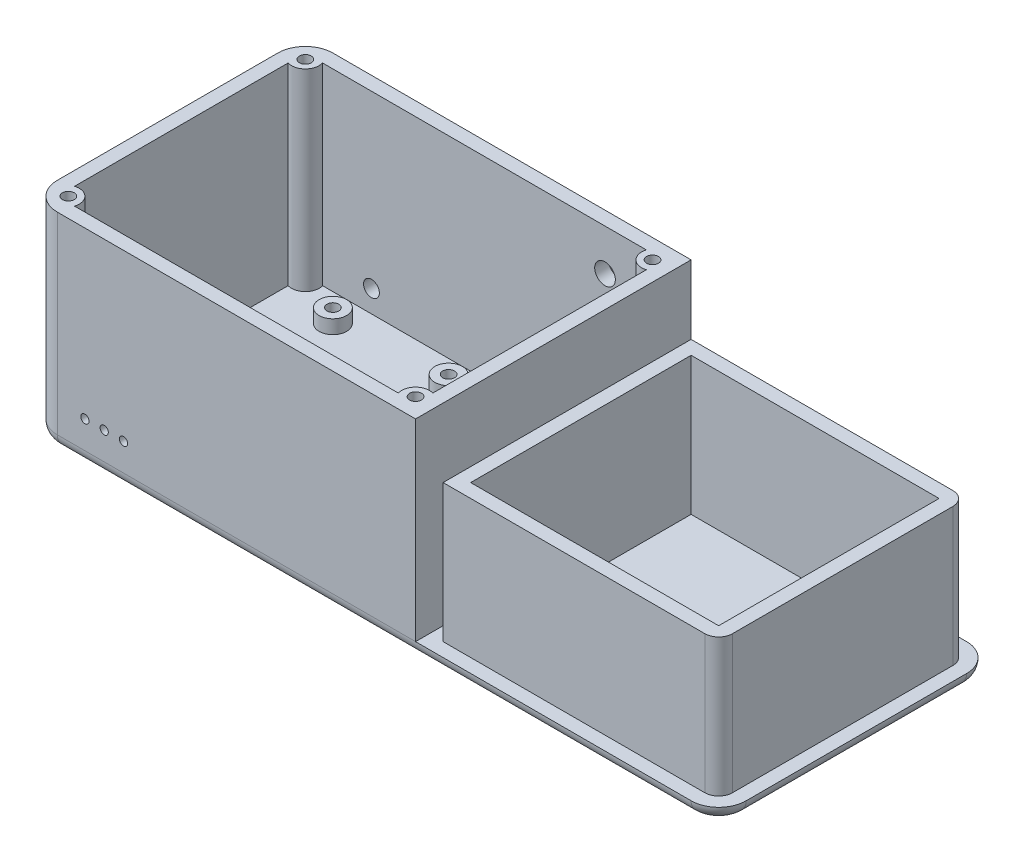
SolidWorks part; units mm, degrees
material "Custom Plastic"
ref_plane "Front Plane" through (0, 0, 0) normal (0, 0, 1) x (1, 0, 0)
ref_plane "Top Plane" through (0, 0, 0) normal (0, 1, 0) x (1, 0, 0)
ref_plane "Right Plane" through (0, 0, 0) normal (1, 0, 0) x (0, 0, -1)
sketch "Sketch1" plane through (0, 0, 0) normal (0, 1, 0) x (1, 0, 0)
  line L1 (-115, -50) -> (115, -50)
  line L2 (-125, -40) -> (-125, 40)
  line L3 (-115, 50) -> (115, 50)
  line L4 (125, -40) -> (125, 40)
  line L5 (-125, -50) -> (125, 50) construction
  line L6 (-125, 50) -> (125, -50) construction
  arc A0 (-115, -50) -> (-125, -40) centre (-115, -40) cw
  arc A1 (115, -50) -> (125, -40) centre (115, -40) ccw
  arc A2 (115, 50) -> (125, 40) centre (115, 40) cw
  arc A3 (-125, 40) -> (-115, 50) centre (-115, 40) cw
  point P0 (0, 0)
  dimension "D3" = 10
  dimension "D1" = 250
  dimension "D2" = 100
extrude "Boss-Extrude1" add sketch "Sketch1" along normal blind 5
fillet "Fillet1" radius 5 8 edges at (0, 0, 50) (122.0711, 0, 47.0711) (125, 0, 0) (122.0711, 0, -47.0711) (0, 0, -50) (-122.0711, 0, -47.0711) (-125, 0, 0) (-122.0711, 0, 47.0711)
sketch "Sketch2" plane through (0, 5, 0) normal (0, 1, 0) x (1, 0, 0)
  line L0 (-115, -45) -> (115, -45)
  line L1 (120, -40) -> (120, 40)
  line L2 (115, 45) -> (-115, 45)
  line L3 (-120, 40) -> (-120, -40)
  line L4 (-115, -50) -> (115, -50)
  line L5 (-115, -50) -> (115, -50)
  line L6 (125, -40) -> (125, 40)
  line L7 (125, -40) -> (125, 40)
  line L12 (15, 50) -> (15, -50)
  line L13 (10, 50) -> (10, -50)
  line L14 (20, 45) -> (20, -45)
  line L15 (115, 40) -> (20, 40)
  line L16 (115, 50) -> (-115, 50)
  line L17 (115, 50) -> (-115, 50)
  line L18 (-125, 40) -> (-125, -40)
  line L19 (-125, 40) -> (-125, -40)
  line L20 (115, 40) -> (115, -40)
  line L21 (115, -40) -> (20, -40)
  line L22 (20, 40) -> (20, -40)
  line L23 (25, 45) -> (25, -45)
  arc A0 (115, -45) -> (120, -40) centre (115, -40) ccw
  arc A1 (120, 40) -> (115, 45) centre (115, 40) ccw
  arc A2 (-115, 45) -> (-120, 40) centre (-115, 40) ccw
  arc A3 (-120, -40) -> (-115, -45) centre (-115, -40) ccw
  arc A4 (-125, -40) -> (-115, -50) centre (-115, -40) ccw
  arc A5 (-125, -40) -> (-115, -50) centre (-115, -40) ccw
  arc A6 (115, -50) -> (125, -40) centre (115, -40) ccw
  arc A7 (115, -50) -> (125, -40) centre (115, -40) ccw
  arc A16 (125, 40) -> (115, 50) centre (115, 40) ccw
  arc A17 (125, 40) -> (115, 50) centre (115, 40) ccw
  arc A18 (-115, 50) -> (-125, 40) centre (-115, 40) ccw
  arc A19 (-115, 50) -> (-125, 40) centre (-115, 40) ccw
  arc M25 (-125, -40) -> (-115, -50) centre (-115, -40) ccw
  line M26 (-115, -50) -> (115, -50)
  line M30 (115, 50) -> (-115, 50)
  arc M31 (-115, 50) -> (-125, 40) centre (-115, 40) ccw
  line M32 (-125, 40) -> (-125, -40)
  dimension "D8" = 5
  dimension "D10" = 5
  dimension "D11" = 5
  dimension "D13" = 5
  dimension "D2" = 5
  dimension "D3" = 5
  dimension "D4" = 5
  dimension "D5" = 5
  dimension "D6" = 5
  dimension "D7" = 5
  dimension "D9" = 5
  dimension "D12" = 5
  dimension "D14" = 5
  dimension "D15" = 140
  dimension "D16" = 5
  dimension "D17" = 5
extrude "Boss-Extrude2" add sketch "Sketch2" along normal blind 70 contours L2 L13 L0 L12 | L0 L13 L5 L12 | A3 L3 A2 L2 L13 L0 M30 M31 M32 M25 M26 | L13 L2 L12 M30 region at (12.5, 5, 47.5) region at (12.5, 5, 0) region at (8.32, 5, 47.5) region at (12.5, 5, -47.5)
extrude "Boss-Extrude3" add sketch "Sketch2<3>" along normal blind 50 contours L23 L15 L14 L21 | L1 A1 L2 L23 L15 L20 L21 L0 A0 | L23 L2 L14 L15 | L23 L21 L14 L0 region at (22.5, 5, 42.5) region at (26.3086, 5, 42.5) region at (22.5, 5, 0) region at (22.5, 5, -42.5)
sketch "Sketch2<3>" plane through (0, 5, 0) normal (0, 1, 0) x (1, 0, 0) same geometry as "Sketch2"
sketch "Sketch3" plane through (0, 75, 0) normal (0, 1, 0) x (1, 0, 0)
  line L0 (15, 50) -> (15, -50) construction
  line L1 (-115, -50) -> (15, -50) construction
  line L3 (15, 50) -> (-115, 50) construction
  circle A0 centre (-118.5355, 43.5355) radius 5
  arc A1 (-115, 45) -> (-120, 40) centre (-115, 40) ccw construction
  circle A2 centre (8.5355, 43.5355) radius 5
  circle A3 centre (8.5355, -43.5355) radius 5
  circle A4 centre (-118.5355, -43.5355) radius 5
  arc A5 (-120, -40) -> (-115, -45) centre (-115, -40) ccw construction
  arc A6 (-125, -40) -> (-115, -50) centre (-115, -40) ccw construction
  arc A7 (15, -40) -> (5, -50) centre (5, -40) cw construction
  arc A8 (5, 50) -> (15, 40) centre (5, 40) cw construction
  point P20 (15, 39.9202)
  point P21 (0, 0)
  point P22 (0, 0)
  point P30 (0, 0)
  dimension "D1" = 10
  dimension "D2" = 10
extrude "Boss-Extrude4" add sketch "Sketch3" against normal up to surface (70 mm away) up to face at (-75.3452, 5, 0)
sketch "Sketch4" plane through (10, 0, 0) normal (-1, 0, 0) x (0, 0, 1)
  line L0 (40, 5) -> (-40, 5) construction
  line L1 (3.75, 10) -> (-3.75, 10)
  line L2 (3.75, 10) -> (3.75, 5)
  line L3 (3.75, 5) -> (-3.75, 5)
  line L4 (-3.75, 10) -> (-3.75, 5)
  line L5 (3.75, 10) -> (-3.75, 5) construction
  line L6 (3.75, 5) -> (-3.75, 10) construction
  point P0 (0, 7.5)
  dimension "D1" = 5
  dimension "D2" = 7.5
extrude "Cut-Extrude1" cut sketch "Sketch4" against normal up to surface (15 mm away) up to face at (25, 30, 0)
sketch "Sketch5" plane through (0, 0, -45) normal (0, 0, 1) x (1, 0, 0)
  line L0 (3.7548, 5) -> (-113.7548, 5) construction
  line L1 (-120, 75) -> (-120, 5) construction
  line L2 (3.7548, 75) -> (-113.7548, 75) construction
  line L3 (3.7548, 75) -> (3.7548, 5) construction
  circle A0 centre (-96, 13) radius 2.875
  circle A1 centre (-11.2452, 60) radius 3.75
  dimension "D1" = 5.75
  dimension "D4" = 7.5
  dimension "D2" = 8
  dimension "D3" = 24
  dimension "D5" = 15
  dimension "D6" = 15
extrude "Cut-Extrude2" cut sketch "Sketch5" against normal up to surface (5 mm away) up to face at (-50, 40, -50)
sketch "Sketch6" plane through (0, 0, 50) normal (0, 0, 1) x (1, 0, 0)
  line L0 (-115, 75) -> (-115, 5) construction
  line L1 (-115, 5) -> (15, 5) construction
  circle A0 centre (-105, 15) radius 1.5
  circle A1 centre (-98, 15) radius 1.5
  circle A2 centre (-91, 15) radius 1.5
  dimension "D1" = 3
  dimension "D5" = 7
  dimension "D2" = 10
  dimension "D3" = 10
  dimension "D4" = 3
extrude "Cut-Extrude3" cut sketch "Sketch6" against normal up to surface (5 mm away) up to face at (-55, 40, 45)
sketch "Sketch8" plane through (0, 5, 0) normal (0, 1, 0) x (1, 0, 0)
  line L0 (-113.7548, -45) -> (3.7548, -45) construction
  line L1 (-120, 38.7548) -> (-120, -38.7548) construction
  circle A0 centre (-100, -25) radius 5
  circle A1 centre (-58, -25) radius 5
  circle A2 centre (-58, 35) radius 5
  circle A3 centre (-100, 35) radius 5
  circle A4 centre (-100, -25) radius 2.15
  circle A5 centre (-58, -25) radius 2.15
  circle A6 centre (-58, 35) radius 2.15
  circle A7 centre (-100, 35) radius 2.15
  dimension "D1" = 10
  dimension "D4" = 20
  dimension "D5" = 60
  dimension "D6" = 42
  dimension "D7" = 20
  dimension "D8" = 4.3
  dimension "D2" = 2
  dimension "D3" = 2
extrude "Boss-Extrude5" add sketch "Sketch8" along normal blind 5
sketch "Sketch9" plane through (0, 75, 0) normal (0, 1, 0) x (1, 0, 0)
  line L0 (-125, 40) -> (-125, -40) construction
  line L1 (15, 50) -> (-115, 50) construction
  line L2 (-55, 45) -> (-55, -45) construction
  line L3 (3.7548, 45) -> (-113.7548, 45) construction
  line L4 (-113.7548, -45) -> (3.7548, -45) construction
  line L5 (-120, 0) -> (10, 0) construction
  line L6 (-120, 38.7548) -> (-120, -38.7548) construction
  line L7 (10, 38.7548) -> (10, -38.7548) construction
  circle A0 centre (-118, 43) radius 2.155
  circle A3 centre (8, 43) radius 2.155
  circle A4 centre (-118, -43) radius 2.155
  circle A5 centre (8, -43) radius 2.155
  dimension "D1" = 7
  dimension "D3" = 4.31
  dimension "D2" = 7
extrude "Cut-Extrude4" cut sketch "Sketch9" against normal blind 5
equation "\"device_length\"=250"
equation "\"D1@Sketch1\"=\"device_length\""
equation "\"device_width\"= 100"
equation "\"D2@Sketch1\"=\"device_width\""
equation "\"device_wall\"=5"
equation "\"D2@Sketch2\"=\"device_wall\""
equation "\"device_base\"= 5"
equation "\"D1@Boss-Extrude1\"=\"device_base\""
equation "\"D1@Fillet1\"=\"device_base\""
equation "\"D3@Sketch2\"=\"device_wall\""
equation "\"D4@Sketch2\"=\"device_wall\""
equation "\"D5@Sketch2\"=\"device_wall\""
equation "\"D6@Sketch2\"=\"device_wall\""
equation "\"D7@Sketch2\"=\"device_wall\""
equation "\"D8@Sketch2\"=\"device_wall\""
equation "\"D9@Sketch2\"=\"device_wall\""
equation "\"D10@Sketch2\"=\"device_wall\""
equation "\"D11@Sketch2\"=\"device_wall\""
equation "\"D12@Sketch2\"=\"device_wall\""
equation "\"D13@Sketch2\"=\"device_wall\""
equation "\"D14@Sketch2\"=\"device_wall\""
equation "\"main_length\"=140"
equation "\"D15@Sketch2\"=\"main_length\""
equation "\"device_height\"=75"
equation "\"D1@Boss-Extrude2\"=\"device_height\"-\"device_base\""
equation "\"D16@Sketch2\"=\"device_wall\""
equation "\"D17@Sketch2\"=\"device_wall\""
equation "\"inner_black_box\"=50"
equation "\"D1@Boss-Extrude3\"=\"inner_black_box\""
equation "\"D6@Sketch5\"=\"D5@Sketch5\""
